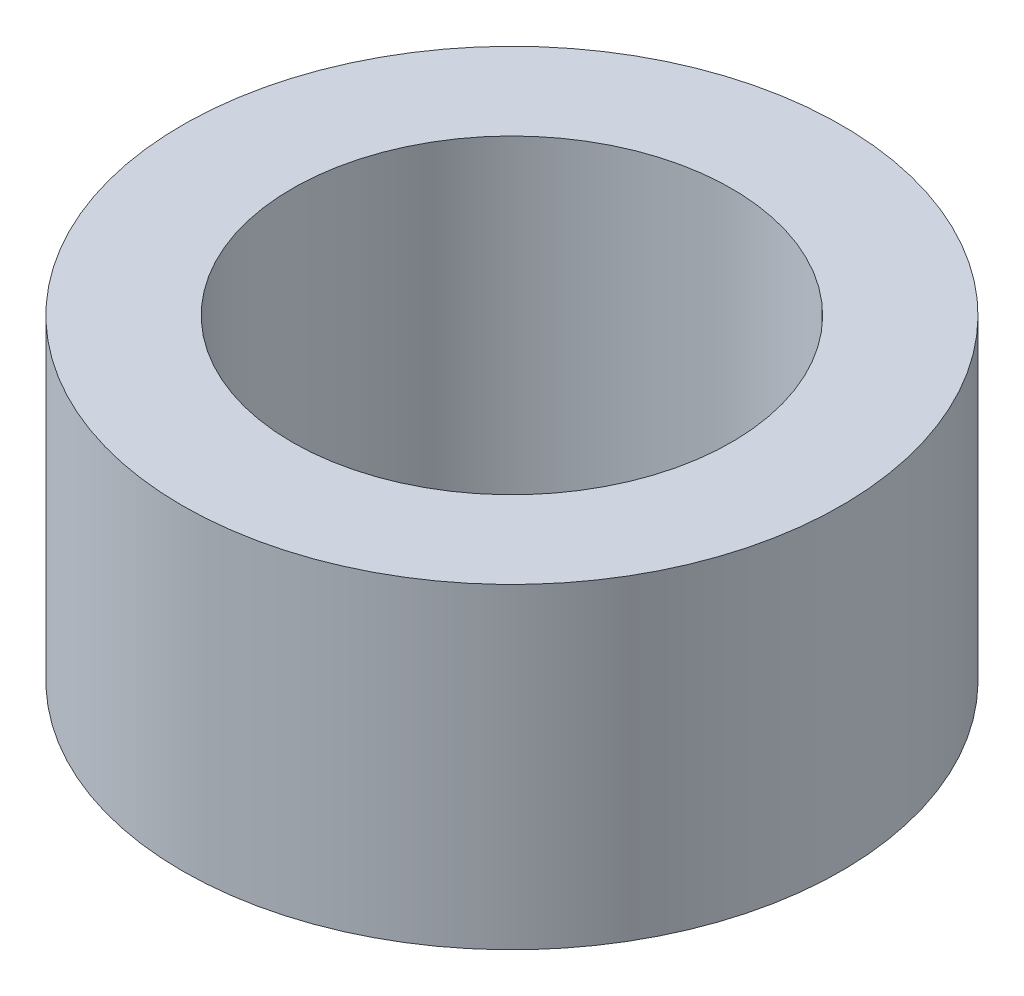
SolidWorks part; units mm, degrees
material "PVC Rigid"
ref_plane "Front Plane" through (0, 0, 0) normal (0, 0, 1) x (1, 0, 0)
ref_plane "Top Plane" through (0, 0, 0) normal (0, 1, 0) x (1, 0, 0)
ref_plane "Right Plane" through (0, 0, 0) normal (1, 0, 0) x (0, 0, -1)
sketch "Sketch1" plane through (0, 0, 0) normal (0, 1, 0) x (1, 0, 0)
  circle A0 centre (0, 0) radius 9.525
  circle A1 centre (0, 0) radius 6.35
  dimension "D1" = 19.05
  dimension "D2" = 12.7
extrude "Boss-Extrude1" add sketch "Sketch1" along normal blind 9.144
